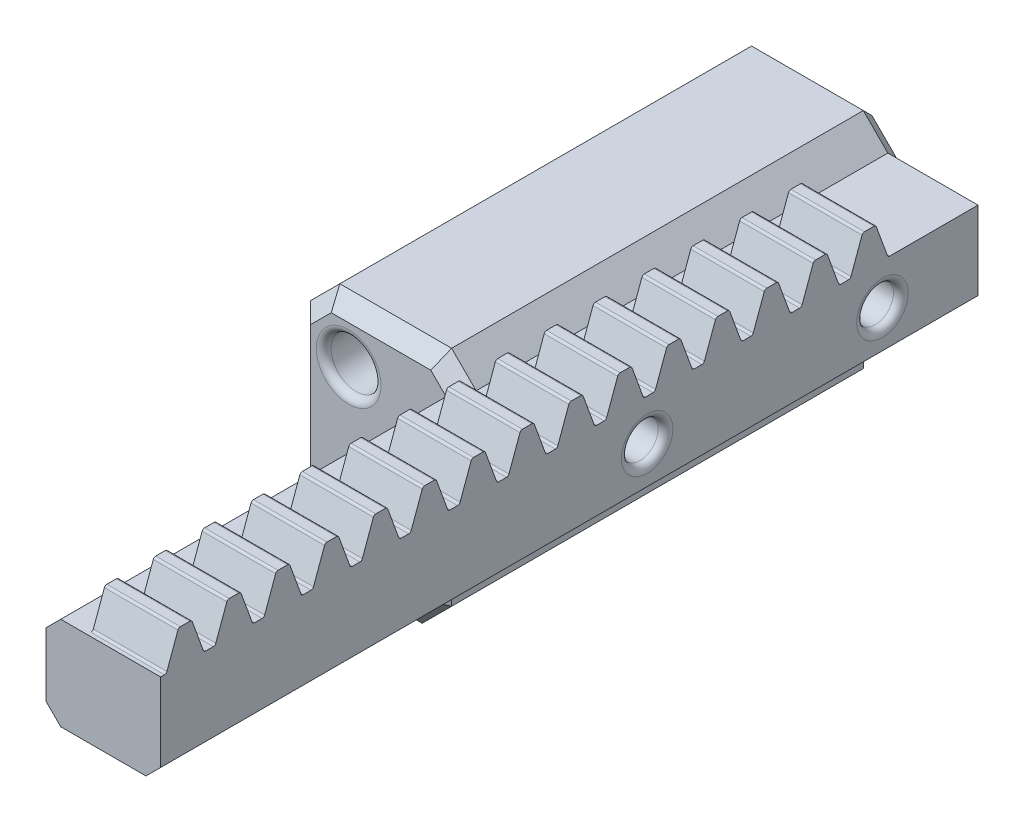
SolidWorks part; units mm, degrees
ref_plane "Plano frontal" through (0, 0, 0) normal (0, 0, 1) x (1, 0, 0)
ref_plane "Plano superior" through (0, 0, 0) normal (0, 1, 0) x (1, 0, 0)
ref_plane "Plano direito" through (0, 0, 0) normal (1, 0, 0) x (0, 0, -1)
sketch "Esboço1" plane through (0, 0, 0) normal (0, 0, 1) x (1, 0, 0)
  line L0 (-6, -10) -> (6, -10) construction
  line L1 (-6, 10) -> (-6, -10) construction
  line L2 (6, 10) -> (-6, 10) construction
  line L3 (6, 10) -> (6, -10) construction
  circle A0 centre (-1, 5) radius 1.5 construction
  circle A1 centre (-1, -5) radius 1.5 construction
sketch "Esboço2" plane through (0, 0, 0) normal (0, 0, 1) x (1, 0, 0)
  line L0 (-1, 5) -> (-1, -5) construction
  line L4 (-4.6, 8.6) -> (5, 8.6)
  line L5 (-4.6, 8.6) -> (-4.6, -8.6)
  line L6 (-4.6, -8.6) -> (5, -8.6)
  line L7 (5, 8.6) -> (5, -8.6)
  circle A10 centre (-1, 5) radius 1.7
  circle A11 centre (-1, 5) radius 1.7
  circle A13 centre (-1, -5) radius 1.7
  circle A14 centre (-1, -5) radius 1.7
  point P0 (-1, 0)
  dimension "D3" = 3.6
  dimension "D4" = 3.6
  dimension "D5" = 6
  dimension "D1" = 0.2
  dimension "D2" = 0.2
extrude "Ressalto-extrusão2" add sketch "Esboço2" along normal blind 30
chamfer "Chanfro1" distance 2 angle 45 3 edges at (-4.6, 8.6, 15) (-4.6, -8.6, 15) (5, -8.6, 15)
ref_plane "Plano1" through (11.8, 0, 0) normal (1, 0, 0) x (0, 0, -1)
sketch "Esboço3" plane through (11.8, 0, 0) normal (1, 0, 0) x (0, 0, -1)
  line L0 (-32.5985, 9.223) -> (-31.3388, 9.223)
  line L1 (-31.1734, 9.1072) -> (-30.4235, 7.0468)
  line L2 (-30.2581, 6.931) -> (-29.7419, 6.931)
  line L3 (-29.5765, 7.0468) -> (-28.8266, 9.1072)
  line L4 (-28.6612, 9.223) -> (-28.0168, 9.223)
  line L5 (-27.8514, 9.1072) -> (-27.1015, 7.0468)
  line L6 (-26.9361, 6.931) -> (-24.1671, 6.931)
  line L7 (-31.2156, 9.223) -> (-31.2156, 5.7646) construction
  line L8 (-28.7844, 9.223) -> (-28.7844, 5.7646) construction
  line L9 (-27.8936, 9.223) -> (-27.8936, 5.7646) construction
  line L10 (-33.5924, 8.165) -> (-24.3137, 8.165) construction
  line L11 (-33.4001, 9.223) -> (-25.1117, 9.223) construction
  line L12 (-30, 6.931) -> (-30, 5.0983) construction
  line L13 (-28.339, 9.223) -> (-28.339, 8.4494) construction
  line L14 (-30, 8.6) -> (-30, -6.6) construction
  line L15 (-30, 8.6) -> (0, 8.6) construction
  arc A0 (-27.1015, 7.0468) -> (-26.9361, 6.931) centre (-26.9361, 7.107) ccw
  arc A1 (-28.0168, 9.223) -> (-27.8514, 9.1072) centre (-28.0168, 9.047) cw
  arc A2 (-28.8266, 9.1072) -> (-28.6612, 9.223) centre (-28.6612, 9.047) cw
  arc A3 (-31.3388, 9.223) -> (-31.1734, 9.1072) centre (-31.3388, 9.047) cw
  arc A4 (-29.7419, 6.931) -> (-29.5765, 7.0468) centre (-29.7419, 7.107) ccw
  arc A5 (-30.4235, 7.0468) -> (-30.2581, 6.931) centre (-30.2581, 7.107) ccw
  circle A6 centre (-46.7178, 16.1) radius 7.935 construction
  point P15 (-30.8305, 8.165)
  point P16 (-29.1695, 8.165)
  point P17 (-27.5085, 8.165)
  dimension "D8" = 0.176
  dimension "D1" = 1.234
  dimension "D2" = 20
  dimension "D3" = 20
  dimension "D4" = 20
  dimension "D5" = 1.058
  dimension "D6" = 1.661
  dimension "D7" = 1.661
  dimension "D9" = 0.435
sketch "Esboço5" plane through (11.8, 0, 0) normal (1, 0, 0) x (0, 0, -1)
  line L0 (-4.5904, 9.1072) -> (-3.8405, 7.0468)
  line L2 (-67.7274, 9.1072) -> (-66.9775, 7.0468)
  line L3 (-68.5372, 9.223) -> (-67.8928, 9.223)
  line L4 (-69.4525, 7.0468) -> (-68.7026, 9.1072)
  line L38 (-1.2674, 9.1072) -> (-0.5175, 7.0468)
  line L39 (-2.0772, 9.223) -> (-1.4328, 9.223)
  line L40 (-2.9925, 7.0468) -> (-2.2426, 9.1072)
  line L45 (0, 6.931) -> (-0.3521, 6.931)
  line L87 (-66.2949, 6.931) -> (-66.8121, 6.931)
  line L90 (-5.4002, 9.223) -> (-4.7558, 9.223)
  line L91 (-6.3155, 7.0468) -> (-5.5656, 9.1072)
  line L92 (-3.1579, 6.931) -> (-3.6751, 6.931)
  line L93 (-7.9134, 9.1072) -> (-7.1635, 7.0468)
  line L94 (-8.7232, 9.223) -> (-8.0788, 9.223)
  line L95 (-9.6385, 7.0468) -> (-8.8886, 9.1072)
  line L96 (-6.4809, 6.931) -> (-6.9981, 6.931)
  line L97 (-11.2364, 9.1072) -> (-10.4865, 7.0468)
  line L98 (-12.0462, 9.223) -> (-11.4018, 9.223)
  line L99 (-12.9615, 7.0468) -> (-12.2116, 9.1072)
  line L100 (-9.8039, 6.931) -> (-10.3211, 6.931)
  line L101 (-14.5594, 9.1072) -> (-13.8095, 7.0468)
  line L102 (-15.3692, 9.223) -> (-14.7248, 9.223)
  line L103 (-16.2845, 7.0468) -> (-15.5346, 9.1072)
  line L104 (-13.1269, 6.931) -> (-13.6441, 6.931)
  line L105 (-17.8824, 9.1072) -> (-17.1325, 7.0468)
  line L106 (-18.6922, 9.223) -> (-18.0478, 9.223)
  line L107 (-19.6075, 7.0468) -> (-18.8576, 9.1072)
  line L108 (-16.4499, 6.931) -> (-16.9671, 6.931)
  line L109 (-21.2054, 9.1072) -> (-20.4555, 7.0468)
  line L110 (-22.0152, 9.223) -> (-21.3708, 9.223)
  line L111 (-22.9305, 7.0468) -> (-22.1806, 9.1072)
  line L112 (-19.7729, 6.931) -> (-20.2901, 6.931)
  line L113 (-24.5284, 9.1072) -> (-23.7785, 7.0468)
  line L114 (-25.3382, 9.223) -> (-24.6938, 9.223)
  line L115 (-26.2535, 7.0468) -> (-25.5036, 9.1072)
  line L116 (-23.0959, 6.931) -> (-23.6131, 6.931)
  line L117 (-27.8514, 9.1072) -> (-27.1015, 7.0468)
  line L118 (-28.6612, 9.223) -> (-28.0168, 9.223)
  line L119 (-29.5765, 7.0468) -> (-28.8266, 9.1072)
  line L120 (-26.4189, 6.931) -> (-26.9361, 6.931)
  line L121 (-31.1744, 9.1072) -> (-30.4245, 7.0468)
  line L122 (-31.9842, 9.223) -> (-31.3398, 9.223)
  line L123 (-32.8995, 7.0468) -> (-32.1496, 9.1072)
  line L124 (-29.7419, 6.931) -> (-30.2591, 6.931)
  line L125 (-34.4974, 9.1072) -> (-33.7475, 7.0468)
  line L126 (-35.3072, 9.223) -> (-34.6628, 9.223)
  line L127 (-36.2225, 7.0468) -> (-35.4726, 9.1072)
  line L128 (-33.0649, 6.931) -> (-33.5821, 6.931)
  line L129 (-37.8204, 9.1072) -> (-37.0705, 7.0468)
  line L130 (-38.6302, 9.223) -> (-37.9858, 9.223)
  line L131 (-39.5455, 7.0468) -> (-38.7956, 9.1072)
  line L132 (-36.3879, 6.931) -> (-36.9051, 6.931)
  line L133 (-41.1434, 9.1072) -> (-40.3935, 7.0468)
  line L134 (-41.9532, 9.223) -> (-41.3088, 9.223)
  line L135 (-42.8685, 7.0468) -> (-42.1186, 9.1072)
  line L136 (-39.7109, 6.931) -> (-40.2281, 6.931)
  line L137 (-44.4664, 9.1072) -> (-43.7165, 7.0468)
  line L138 (-45.2762, 9.223) -> (-44.6318, 9.223)
  line L139 (-46.1915, 7.0468) -> (-45.4416, 9.1072)
  line L140 (-43.0339, 6.931) -> (-43.5511, 6.931)
  line L141 (-47.7894, 9.1072) -> (-47.0395, 7.0468)
  line L142 (-48.5992, 9.223) -> (-47.9548, 9.223)
  line L143 (-49.5145, 7.0468) -> (-48.7646, 9.1072)
  line L144 (-46.3569, 6.931) -> (-46.8741, 6.931)
  line L145 (-51.1124, 9.1072) -> (-50.3625, 7.0468)
  line L146 (-51.9222, 9.223) -> (-51.2778, 9.223)
  line L147 (-52.8375, 7.0468) -> (-52.0876, 9.1072)
  line L148 (-49.6799, 6.931) -> (-50.1971, 6.931)
  line L149 (-54.4354, 9.1072) -> (-53.6855, 7.0468)
  line L150 (-55.2452, 9.223) -> (-54.6008, 9.223)
  line L151 (-56.1605, 7.0468) -> (-55.4106, 9.1072)
  line L152 (-53.0029, 6.931) -> (-53.5201, 6.931)
  line L153 (-57.7584, 9.1072) -> (-57.0085, 7.0468)
  line L154 (-58.5682, 9.223) -> (-57.9238, 9.223)
  line L155 (-59.4835, 7.0468) -> (-58.7336, 9.1072)
  line L156 (-56.3259, 6.931) -> (-56.8431, 6.931)
  line L157 (-61.0814, 9.1072) -> (-60.3315, 7.0468)
  line L158 (-61.8912, 9.223) -> (-61.2468, 9.223)
  line L159 (-62.8065, 7.0468) -> (-62.0566, 9.1072)
  line L160 (-59.6489, 6.931) -> (-60.1661, 6.931)
  line L161 (-64.4044, 9.1072) -> (-63.6545, 7.0468)
  line L162 (-65.2142, 9.223) -> (-64.5698, 9.223)
  line L163 (-66.1295, 7.0468) -> (-65.3796, 9.1072)
  line L164 (-62.9719, 6.931) -> (-63.4891, 6.931)
  line L166 (-71.0504, 9.1072) -> (-70.3005, 7.0468)
  line L168 (-71.8602, 9.223) -> (-71.2158, 9.223)
  line L170 (-72.7755, 7.0468) -> (-72.0256, 9.1072)
  line L171 (-69.6179, 6.931) -> (-70.1351, 6.931)
  line L172 (-74.3734, 9.1072) -> (-73.6235, 7.0468)
  line L173 (-75.1832, 9.223) -> (-74.5388, 9.223)
  line L174 (-76.0985, 7.0468) -> (-75.3486, 9.1072)
  line L175 (-72.9409, 6.931) -> (-73.4581, 6.931)
  line L176 (-77.6964, 9.1072) -> (-76.9465, 7.0468)
  line L177 (-78.5062, 9.223) -> (-77.8618, 9.223)
  line L178 (-79.4215, 7.0468) -> (-78.6716, 9.1072)
  line L179 (-76.2639, 6.931) -> (-76.7811, 6.931)
  line L180 (-81.0194, 9.1072) -> (-80.2695, 7.0468)
  line L181 (-81.8292, 9.223) -> (-81.1848, 9.223)
  line L182 (-82.7445, 7.0468) -> (-81.9946, 9.1072)
  line L183 (-79.5869, 6.931) -> (-80.1041, 6.931)
  line L184 (-82.9099, 6.931) -> (-83.4099, 6.931)
  line L186 (0, 6.931) -> (0, 0.6)
  line L187 (-83.4099, 6.931) -> (-83.4099, 0.6)
  line L188 (-83.4099, 0.6) -> (0, 0.6)
  line L189 (-30, 8.6) -> (0, 8.6) construction
  arc A36 (-0.5175, 7.0468) -> (-0.3521, 6.931) centre (-0.3521, 7.107) ccw
  arc A37 (-1.2674, 9.1072) -> (-1.4328, 9.223) centre (-1.4328, 9.047) ccw
  arc A38 (-2.0772, 9.223) -> (-2.2426, 9.1072) centre (-2.0772, 9.047) ccw
  arc A39 (-3.1579, 6.931) -> (-2.9925, 7.0468) centre (-3.1579, 7.107) ccw
  arc A84 (-3.8405, 7.0468) -> (-3.6751, 6.931) centre (-3.6751, 7.107) ccw
  arc A85 (-4.5904, 9.1072) -> (-4.7558, 9.223) centre (-4.7558, 9.047) ccw
  arc A86 (-5.4002, 9.223) -> (-5.5656, 9.1072) centre (-5.4002, 9.047) ccw
  arc A87 (-6.4809, 6.931) -> (-6.3155, 7.0468) centre (-6.4809, 7.107) ccw
  arc A88 (-7.1635, 7.0468) -> (-6.9981, 6.931) centre (-6.9981, 7.107) ccw
  arc A89 (-7.9134, 9.1072) -> (-8.0788, 9.223) centre (-8.0788, 9.047) ccw
  arc A90 (-8.7232, 9.223) -> (-8.8886, 9.1072) centre (-8.7232, 9.047) ccw
  arc A91 (-9.8039, 6.931) -> (-9.6385, 7.0468) centre (-9.8039, 7.107) ccw
  arc A92 (-10.4865, 7.0468) -> (-10.3211, 6.931) centre (-10.3211, 7.107) ccw
  arc A93 (-11.2364, 9.1072) -> (-11.4018, 9.223) centre (-11.4018, 9.047) ccw
  arc A94 (-12.0462, 9.223) -> (-12.2116, 9.1072) centre (-12.0462, 9.047) ccw
  arc A95 (-13.1269, 6.931) -> (-12.9615, 7.0468) centre (-13.1269, 7.107) ccw
  arc A96 (-13.8095, 7.0468) -> (-13.6441, 6.931) centre (-13.6441, 7.107) ccw
  arc A97 (-14.5594, 9.1072) -> (-14.7248, 9.223) centre (-14.7248, 9.047) ccw
  arc A98 (-15.3692, 9.223) -> (-15.5346, 9.1072) centre (-15.3692, 9.047) ccw
  arc A99 (-16.4499, 6.931) -> (-16.2845, 7.0468) centre (-16.4499, 7.107) ccw
  arc A100 (-17.1325, 7.0468) -> (-16.9671, 6.931) centre (-16.9671, 7.107) ccw
  arc A101 (-17.8824, 9.1072) -> (-18.0478, 9.223) centre (-18.0478, 9.047) ccw
  arc A102 (-18.6922, 9.223) -> (-18.8576, 9.1072) centre (-18.6922, 9.047) ccw
  arc A103 (-19.7729, 6.931) -> (-19.6075, 7.0468) centre (-19.7729, 7.107) ccw
  arc A104 (-20.4555, 7.0468) -> (-20.2901, 6.931) centre (-20.2901, 7.107) ccw
  arc A105 (-21.2054, 9.1072) -> (-21.3708, 9.223) centre (-21.3708, 9.047) ccw
  arc A106 (-22.0152, 9.223) -> (-22.1806, 9.1072) centre (-22.0152, 9.047) ccw
  arc A107 (-23.0959, 6.931) -> (-22.9305, 7.0468) centre (-23.0959, 7.107) ccw
  arc A108 (-23.7785, 7.0468) -> (-23.6131, 6.931) centre (-23.6131, 7.107) ccw
  arc A109 (-24.5284, 9.1072) -> (-24.6938, 9.223) centre (-24.6938, 9.047) ccw
  arc A110 (-25.3382, 9.223) -> (-25.5036, 9.1072) centre (-25.3382, 9.047) ccw
  arc A111 (-26.4189, 6.931) -> (-26.2535, 7.0468) centre (-26.4189, 7.107) ccw
  arc A112 (-27.1015, 7.0468) -> (-26.9361, 6.931) centre (-26.9361, 7.107) ccw
  arc A113 (-27.8514, 9.1072) -> (-28.0168, 9.223) centre (-28.0168, 9.047) ccw
  arc A114 (-28.6612, 9.223) -> (-28.8266, 9.1072) centre (-28.6612, 9.047) ccw
  arc A115 (-29.7419, 6.931) -> (-29.5765, 7.0468) centre (-29.7419, 7.107) ccw
  arc A116 (-30.4245, 7.0468) -> (-30.2591, 6.931) centre (-30.2591, 7.107) ccw
  arc A117 (-31.1744, 9.1072) -> (-31.3398, 9.223) centre (-31.3398, 9.047) ccw
  arc A118 (-31.9842, 9.223) -> (-32.1496, 9.1072) centre (-31.9842, 9.047) ccw
  arc A119 (-33.0649, 6.931) -> (-32.8995, 7.0468) centre (-33.0649, 7.107) ccw
  arc A120 (-33.7475, 7.0468) -> (-33.5821, 6.931) centre (-33.5821, 7.107) ccw
  arc A121 (-34.4974, 9.1072) -> (-34.6628, 9.223) centre (-34.6628, 9.047) ccw
  arc A122 (-35.3072, 9.223) -> (-35.4726, 9.1072) centre (-35.3072, 9.047) ccw
  arc A123 (-36.3879, 6.931) -> (-36.2225, 7.0468) centre (-36.3879, 7.107) ccw
  arc A124 (-37.0705, 7.0468) -> (-36.9051, 6.931) centre (-36.9051, 7.107) ccw
  arc A125 (-37.8204, 9.1072) -> (-37.9858, 9.223) centre (-37.9858, 9.047) ccw
  arc A126 (-38.6302, 9.223) -> (-38.7956, 9.1072) centre (-38.6302, 9.047) ccw
  arc A127 (-39.7109, 6.931) -> (-39.5455, 7.0468) centre (-39.7109, 7.107) ccw
  arc A128 (-40.3935, 7.0468) -> (-40.2281, 6.931) centre (-40.2281, 7.107) ccw
  arc A129 (-41.1434, 9.1072) -> (-41.3088, 9.223) centre (-41.3088, 9.047) ccw
  arc A130 (-41.9532, 9.223) -> (-42.1186, 9.1072) centre (-41.9532, 9.047) ccw
  arc A131 (-43.0339, 6.931) -> (-42.8685, 7.0468) centre (-43.0339, 7.107) ccw
  arc A132 (-43.7165, 7.0468) -> (-43.5511, 6.931) centre (-43.5511, 7.107) ccw
  arc A133 (-44.4664, 9.1072) -> (-44.6318, 9.223) centre (-44.6318, 9.047) ccw
  arc A134 (-45.2762, 9.223) -> (-45.4416, 9.1072) centre (-45.2762, 9.047) ccw
  arc A135 (-46.3569, 6.931) -> (-46.1915, 7.0468) centre (-46.3569, 7.107) ccw
  arc A136 (-47.0395, 7.0468) -> (-46.8741, 6.931) centre (-46.8741, 7.107) ccw
  arc A137 (-47.7894, 9.1072) -> (-47.9548, 9.223) centre (-47.9548, 9.047) ccw
  arc A138 (-48.5992, 9.223) -> (-48.7646, 9.1072) centre (-48.5992, 9.047) ccw
  arc A139 (-49.6799, 6.931) -> (-49.5145, 7.0468) centre (-49.6799, 7.107) ccw
  arc A140 (-50.3625, 7.0468) -> (-50.1971, 6.931) centre (-50.1971, 7.107) ccw
  arc A141 (-51.1124, 9.1072) -> (-51.2778, 9.223) centre (-51.2778, 9.047) ccw
  arc A142 (-51.9222, 9.223) -> (-52.0876, 9.1072) centre (-51.9222, 9.047) ccw
  arc A143 (-53.0029, 6.931) -> (-52.8375, 7.0468) centre (-53.0029, 7.107) ccw
  arc A144 (-53.6855, 7.0468) -> (-53.5201, 6.931) centre (-53.5201, 7.107) ccw
  arc A145 (-54.4354, 9.1072) -> (-54.6008, 9.223) centre (-54.6008, 9.047) ccw
  arc A146 (-55.2452, 9.223) -> (-55.4106, 9.1072) centre (-55.2452, 9.047) ccw
  arc A147 (-56.3259, 6.931) -> (-56.1605, 7.0468) centre (-56.3259, 7.107) ccw
  arc A148 (-57.0085, 7.0468) -> (-56.8431, 6.931) centre (-56.8431, 7.107) ccw
  arc A149 (-57.7584, 9.1072) -> (-57.9238, 9.223) centre (-57.9238, 9.047) ccw
  arc A150 (-58.5682, 9.223) -> (-58.7336, 9.1072) centre (-58.5682, 9.047) ccw
  arc A151 (-59.6489, 6.931) -> (-59.4835, 7.0468) centre (-59.6489, 7.107) ccw
  arc A152 (-60.3315, 7.0468) -> (-60.1661, 6.931) centre (-60.1661, 7.107) ccw
  arc A153 (-61.0814, 9.1072) -> (-61.2468, 9.223) centre (-61.2468, 9.047) ccw
  arc A154 (-61.8912, 9.223) -> (-62.0566, 9.1072) centre (-61.8912, 9.047) ccw
  arc A155 (-62.9719, 6.931) -> (-62.8065, 7.0468) centre (-62.9719, 7.107) ccw
  arc A156 (-63.6545, 7.0468) -> (-63.4891, 6.931) centre (-63.4891, 7.107) ccw
  arc A157 (-64.4044, 9.1072) -> (-64.5698, 9.223) centre (-64.5698, 9.047) ccw
  arc A158 (-65.2142, 9.223) -> (-65.3796, 9.1072) centre (-65.2142, 9.047) ccw
  arc A159 (-66.2949, 6.931) -> (-66.1295, 7.0468) centre (-66.2949, 7.107) ccw
  arc A160 (-66.9775, 7.0468) -> (-66.8121, 6.931) centre (-66.8121, 7.107) ccw
  arc A161 (-67.7274, 9.1072) -> (-67.8928, 9.223) centre (-67.8928, 9.047) ccw
  arc A162 (-68.5372, 9.223) -> (-68.7026, 9.1072) centre (-68.5372, 9.047) ccw
  arc A163 (-69.6179, 6.931) -> (-69.4525, 7.0468) centre (-69.6179, 7.107) ccw
  arc A164 (-70.3005, 7.0468) -> (-70.1351, 6.931) centre (-70.1351, 7.107) ccw
  arc A165 (-71.0504, 9.1072) -> (-71.2158, 9.223) centre (-71.2158, 9.047) ccw
  arc A166 (-71.8602, 9.223) -> (-72.0256, 9.1072) centre (-71.8602, 9.047) ccw
  arc A167 (-72.9409, 6.931) -> (-72.7755, 7.0468) centre (-72.9409, 7.107) ccw
  arc A168 (-73.6235, 7.0468) -> (-73.4581, 6.931) centre (-73.4581, 7.107) ccw
  arc A169 (-74.3734, 9.1072) -> (-74.5388, 9.223) centre (-74.5388, 9.047) ccw
  arc A170 (-75.1832, 9.223) -> (-75.3486, 9.1072) centre (-75.1832, 9.047) ccw
  arc A171 (-76.2639, 6.931) -> (-76.0985, 7.0468) centre (-76.2639, 7.107) ccw
  arc A172 (-76.9465, 7.0468) -> (-76.7811, 6.931) centre (-76.7811, 7.107) ccw
  arc A173 (-77.6964, 9.1072) -> (-77.8618, 9.223) centre (-77.8618, 9.047) ccw
  arc A174 (-78.5062, 9.223) -> (-78.6716, 9.1072) centre (-78.5062, 9.047) ccw
  arc A175 (-79.5869, 6.931) -> (-79.4215, 7.0468) centre (-79.5869, 7.107) ccw
  arc A176 (-80.2695, 7.0468) -> (-80.1041, 6.931) centre (-80.1041, 7.107) ccw
  arc A177 (-81.0194, 9.1072) -> (-81.1848, 9.223) centre (-81.1848, 9.047) ccw
  arc A178 (-81.8292, 9.223) -> (-81.9946, 9.1072) centre (-81.8292, 9.047) ccw
  arc A179 (-82.9099, 6.931) -> (-82.7445, 7.0468) centre (-82.9099, 7.107) ccw
  dimension "D3" = 8
  dimension "D1" = 20
extrude "Ressalto-extrusão3" add sketch "Esboço5" against normal blind 4 and the other way blind 1
sketch "Esboço6" plane through (7.8, 0, 0) normal (-1, 0, 0) x (0, 0, 1)
  line L0 (0, 6.931) -> (0.3521, 6.931) construction
  line L1 (30, 0.6) -> (0, 0.6)
  line L2 (30, 0.6) -> (30, 6.931)
  line L3 (30, 6.931) -> (0, 6.931)
  line L4 (0, 0.6) -> (0, 6.931)
  line L5 (0, 6.6) -> (0, 8.6) construction
  line L8 (83.4099, 0.6) -> (0, 0.6) construction
extrude "Ressalto-extrusão5" add sketch "Esboço6" along normal up to surface (2.8 mm away) contours L3 L4 L1 L2 up to face at (5, 1, 15)
chamfer "Chanfro3" distance 1.67 angle 45 1 edges at (5, 6.931, 15)
fillet "Filete1" radius 0.5 4 edges at (0.7, 5, 30) (0.7, 5, 0) (0.7, -5, 30) (0.7, -5, 0)
sketch "Esboço10" plane through (12.8, 0, 0) normal (1, 0, 0) x (0, 0, -1)
  line L0 (-73.1995, 6.931) -> (-73.1995, 7.6937) construction
  line L1 (-84.1532, 10.4639) -> (-73.1995, 10.4639)
  line L2 (-84.1532, 10.4639) -> (-84.1532, -1.511)
  line L3 (-84.1532, -1.511) -> (-73.1995, -1.511)
  line L4 (-73.1995, 10.4639) -> (-73.1995, -1.511)
  line L5 (-72.9409, 6.931) -> (-73.4581, 6.931) construction
extrude "Corte-extrusão3" cut sketch "Esboço10" against normal blind 5
chamfer "Chanfro6" distance 7.8 angle 30 1 edges at (5, 0.6, 15)
sketch "Esboço11" plane through (0, 0, 30) normal (0, 0, 1) x (1, 0, 0)
  line L1 (5, -3.9033) -> (12.8, -3.9033)
  line L2 (5, -3.9033) -> (5, 0.6)
  line L3 (5, 0.6) -> (12.8, 0.6)
  line L4 (12.8, -3.9033) -> (12.8, 0.6)
extrude "Corte-extrusão4" cut sketch "Esboço11" along normal blind 54
sketch "Esboço14" plane through (12.8, 0, 0) normal (1, 0, 0) x (0, 0, -1)
  line L1 (-75.4025, 10.1261) -> (-56.5845, 10.1261)
  line L2 (-75.4025, 10.1261) -> (-75.4025, -2.2163)
  line L3 (-75.4025, -2.2163) -> (-56.5845, -2.2163)
  line L4 (-56.5845, 10.1261) -> (-56.5845, -2.2163)
extrude "Corte-extrusão5" cut sketch "Esboço14" against normal blind 7
sketch "Esboço15" plane through (7.8, 0, 0) normal (-1, 0, 0) x (0, 0, 1)
  line L13 (56.5845, 0.6) -> (30, 0.6)
  line L14 (56.5845, 0.6) -> (56.5845, 6.931)
  line L15 (56.5845, 6.931) -> (30, 6.931)
  line L16 (30, 0.6) -> (30, 6.931)
  line L17 (56.5845, 0.6) -> (30, 0.6) construction
extrude "Ressalto-extrusão7" add sketch "Esboço15" along normal up to vertex (2.799 mm away)
chamfer "Chanfro11" distance 1 angle 45 2 edges at (5.001, 0.6, 43.2922) (5.001, 6.931, 43.2922)
sketch "Esboço17" plane through (12.8, 0, 0) normal (1, 0, 0) x (0, 0, -1)
  line L0 (-6.7395, 6.931) -> (-6.7395, 7.9739) construction
  line L1 (-6.4809, 6.931) -> (-6.9981, 6.931) construction
  line L3 (-6.9981, 6.931) -> (0.6998, 6.931)
  line L4 (-6.9981, 6.931) -> (-6.9981, 10.3543)
  line L5 (-6.9981, 10.3543) -> (0.6998, 10.3543)
  line L6 (0.6998, 6.931) -> (0.6998, 10.3543)
extrude "Corte-extrusão7" cut sketch "Esboço17" against normal blind 5.5
chamfer "Chanfro12" distance 1 angle 45 20 edges at (-3.6, 7.6, 30) (-3.6, 7.6, 0) (-4.6, 0, 30) (-4.6, 0, 0) (-3.6, -7.6, 30) (-3.6, -7.6, 0) (0.2, -8.6, 0) (0.2, -8.6, 30) (4, -7.6, 30) (4, -7.6, 0) (5, -5.2517, 0) (5, -5.2517, 30) (8.9, -1.6517, 30) (8.9, -1.6517, 0) (12.8, 3.7655, 0) (9.735, 6.931, 0) (5.8355, 7.7655, 30) (5.8355, 7.7655, 0) (1.2005, 8.6, 0) (1.2005, 8.6, 30)
sketch "Esboço18" plane through (12.8, 0, 0) normal (1, 0, 0) x (0, 0, -1)
  line L0 (-1, 4.131) -> (-30, 4.131) construction
  line L2 (-30, 4.131) -> (-30, 0.6) construction
  line L3 (-15.5, 4.131) -> (-15.5, 6.2108) construction
  line L4 (-1, 6.931) -> (-6.9981, 6.931) construction
  circle A0 centre (-23.5, 4.131) radius 1.25
  circle A1 centre (-7.5, 4.131) radius 1.25
  dimension "D3" = 2.5
  dimension "D4" = 2.5
  dimension "D1" = 8
  dimension "D2" = 8
  dimension "D5" = 2.8
extrude "Corte-extrusão8" cut sketch "Esboço18" against normal blind 8.5
fillet "Filete2" radius 0.5 2 edges at (12.8, 5.381, 7.5) (12.8, 5.381, 23.5)
sketch "Esboço19" plane through (0, 0, 56.5845) normal (0, 0, 1) x (1, 0, 0)
  line L6 (9.486, -1.714) -> (13.2672, 2.0672)
  line L7 (9.486, -1.714) -> (9.486, -2.5221)
  line L8 (9.486, -2.5221) -> (13.2672, -2.5221)
  line L9 (13.2672, -2.5221) -> (13.2672, 2.0672)
extrude "Corte-extrusão9" cut sketch "Esboço19" against normal blind 61.5
